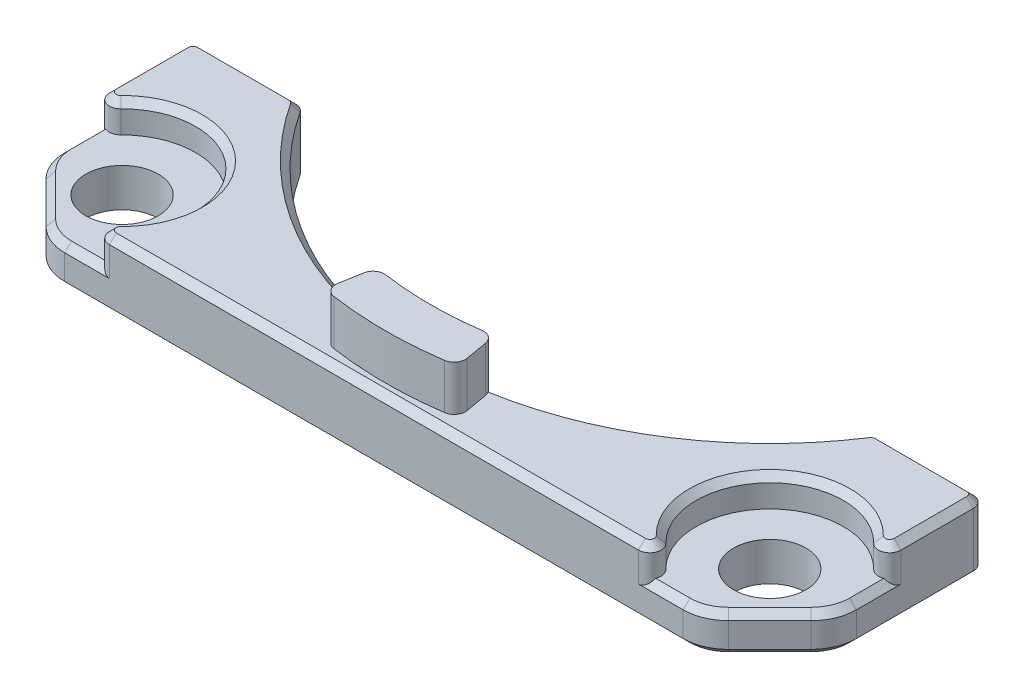
SolidWorks part; units mm, degrees
material "6061 合金"
ref_plane "前视基准面" through (0, 0, 0) normal (0, 0, 1) x (1, 0, 0)
ref_plane "上视基准面" through (0, 0, 0) normal (0, 1, 0) x (1, 0, 0)
ref_plane "右视基准面" through (0, 0, 0) normal (1, 0, 0) x (0, 0, -1)
other "Configuration Table"
sketch "草图1" plane through (0, 0, 0) normal (0, 1, 0) x (1, 0, 0)
  line L0 (-12.6886, -8) -> (-17.5, -8)
  line L1 (-17.5, 17.5) -> (17.5, 17.5) construction
  line L2 (-17.5, 17.5) -> (-17.5, -17.5) construction
  line L3 (-17.5, -17.5) -> (17.5, -17.5) construction
  line L4 (17.5, 17.5) -> (17.5, -17.5) construction
  line L5 (-17.5, 17.5) -> (17.5, -17.5) construction
  line L6 (-17.5, -17.5) -> (17.5, 17.5) construction
  line L7 (12.6886, -8) -> (17.5, -8)
  line L8 (-17.5, -8) -> (-17.5, -17.5)
  line L9 (-17.5, -17.5) -> (17.5, -17.5)
  line L10 (17.5, -17.5) -> (17.5, -8)
  arc A0 (-12.6886, -8) -> (12.6886, -8) centre (0, 0) ccw
  point P0 (0, 0)
  dimension "D3" = 30
  dimension "D1" = 35
  dimension "D2" = 35
  dimension "D4" = 8
extrude "凸台-拉伸1" add sketch "草图1" along normal blind 3
chamfer "倒角1" distance 3 angle 45 2 edges at (-17.5, 1.5, 17.5) (17.5, 1.5, 17.5)
sketch "草图2" plane through (0, 3, 0) normal (0, 1, 0) x (1, 0, 0)
  line L0 (0, 0) -> (14.3189, -14.3189) construction
  line L1 (0, 0) -> (0, -20.25) construction
  circle A0 centre (0, 0) radius 20.25 construction
  circle A1 centre (14.3189, -14.3189) radius 1.6
  circle A2 centre (-14.3189, -14.3189) radius 1.6
  dimension "D1" = 40.5
  dimension "D3" = 3.2
  dimension "D2" = 45
extrude "切除-拉伸1" cut sketch "草图2" against normal blind 3
sketch "草图3" plane through (0, 3, 0) normal (0, 1, 0) x (1, 0, 0)
  line L0 (-2.6047, -14.7721) -> (-2.952, -16.7417)
  line L1 (-14.5, -17.5) -> (14.5, -17.5) construction
  line L2 (0, 0) -> (0, -17.5) construction
  line L6 (2.6047, -14.7721) -> (2.952, -16.7417)
  arc A0 (-12.6886, -8) -> (12.6886, -8) centre (0, 0) ccw construction
  arc A1 (-2.6047, -14.7721) -> (2.6047, -14.7721) centre (0, 0) ccw
  arc A3 (-2.6047, -14.7721) -> (2.6047, -14.7721) centre (0, 0) ccw
  arc A4 (-2.952, -16.7417) -> (2.952, -16.7417) centre (0, 0) ccw
  point P10 (-2.952, -16.7417)
  point P12 (2.952, -16.7417)
  arc M12 (12.6886, -8) -> (-12.6886, -8) centre (0, 0) cw
  dimension "D2" = 34
  dimension "D1" = 10
  dimension "D3" = 10
extrude "凸台-拉伸2" add sketch "草图3" along normal blind 2 contours L2 A3 L0 A4 | L2 A4 L6 M12 region at (-1.3945, 3, 15.9396) region at (1.3945, 3, 15.9396)
sketch "草图5" plane through (0, 3, 0) normal (0, 1, 0) x (1, 0, 0)
  circle A0 centre (-14.3189, -14.3189) radius 3.25
  circle A1 centre (14.3189, -14.3189) radius 3.25
  dimension "D1" = 6.5
  dimension "D2" = 6.5
extrude "切除-拉伸2" cut sketch "草图5" against normal blind 1.3
fillet "圆角1" radius 0.5 8 edges at (12.6886, 1.5, 8) (-12.6886, 1.5, 8) (-17.5, 1.5, 8) (17.5, 1.5, 8) (17.5, 2.35, 13.6532) (13.6532, 2.35, 17.5) (-13.6532, 2.35, 17.5) (-17.5, 2.35, 13.6532)
fillet "圆角5" radius 0.5 4 edges at (-2.6047, 4, 14.7721) (2.6047, 4, 14.7721) (2.952, 4, 16.7417) (-2.952, 4, 16.7417)
fillet "圆角4" radius 2 4 edges at (17.5, 0.85, 14.5) (14.5, 0.85, 17.5) (-14.5, 0.85, 17.5) (-17.5, 0.85, 14.5)
chamfer "倒角2" distance 0.3 angle 45 33 edges at (-17.5, 3, 10.0985) (-17.1888, 3, 12.16) (-17.3536, 3, 8.1464) (-12.0208, 3, 12.0208) (-14.9807, 3, 8) (-12.16, 3, 17.1888) (-12.7239, 3, 8.0601) (-8.0479, 3, 12.6583) (12.16, 3, 17.1888) (12.0208, 3, 12.0208) (17.1888, 3, 12.16) (17.5, 3, 10.0985) (17.3536, 3, 8.1464) (14.9807, 3, 8) (12.7239, 3, 8.0601) (8.0479, 3, 12.6583) (17.3536, 0, 8.1464) (14.9807, 0, 8) (12.7239, 0, 8.0601) (0, 0, 15) (-12.7239, 0, 8.0601) (-14.9807, 0, 8) (-17.3536, 0, 8.1464) (-17.5, 0, 11.0858) (-17.3478, 0, 14.4369) (-16, 0, 16) (-14.4369, 0, 17.3478) (0, 0, 17.5) (14.4369, 0, 17.3478) (16, 0, 16) (17.3478, 0, 14.4369) (17.5, 0, 11.0858) (0, 3, 17.5)
chamfer "倒角3" distance 0.3 angle 45 10 edges at (17.5, 1.7, 12.6843) (17.3478, 1.7, 14.4369) (16, 1.7, 16) (14.4369, 1.7, 17.3478) (12.6843, 1.7, 17.5) (-12.6843, 1.7, 17.5) (-14.4369, 1.7, 17.3478) (-16, 1.7, 16) (-17.3478, 1.7, 14.4369) (-17.5, 1.7, 12.6843)
